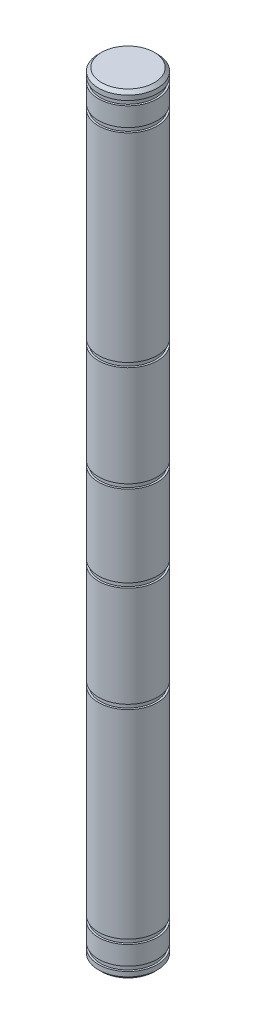
SolidWorks part; units mm, degrees
ref_plane "Front" through (0, 0, 0) normal (0, 0, 1) x (1, 0, 0)
ref_plane "Top" through (0, 0, 0) normal (0, 1, 0) x (1, 0, 0)
ref_plane "Right" through (0, 0, 0) normal (1, 0, 0) x (0, 0, -1)
ref_axis "side-side" through (80.9, 0, 0) along (-1, 0, 0)
ref_axis "up-down" through (0, 50, 0) along (0, -1, 0)
ref_axis "front-back" through (0, 0, -80.9) along (0, 0, 1)
sketch "Sketch1" plane through (0, 0, 0) normal (0, 0, 1) x (1, 0, 0)
  line L0 (-4.7625, 60.2234) -> (-4.7625, 57.1754)
  line L1 (0, 62.23) -> (-4.7625, 62.23)
  line L2 (0, 62.23) -> (0, -62.23)
  line L3 (0, -62.23) -> (-4.7625, -62.23)
  line L4 (-4.7625, 62.23) -> (-4.7625, 60.96)
  line L5 (-4.7625, 60.96) -> (-4.4577, 60.96)
  line L6 (-4.7625, -60.96) -> (-4.7625, -62.23)
  line L7 (-4.7625, 60.2234) -> (-4.4577, 60.2234)
  line L8 (-4.4577, 60.96) -> (-4.4577, 60.2234)
  line L9 (-4.7625, -60.2234) -> (-4.4577, -60.2234)
  line L10 (0, 62.23) -> (0, 13.3378) construction
  line L11 (-4.7625, -60.96) -> (-4.4577, -60.96)
  line L12 (-4.4577, -60.2234) -> (-4.4577, -60.96)
  line L13 (97.3746, 0) -> (-2.6254, 0) construction
  line L14 (-4.7625, 57.1754) -> (-4.4577, 57.1754)
  line L15 (-4.7625, 56.4388) -> (-4.7625, 24.2951)
  line L16 (-4.7625, 56.4388) -> (-4.4577, 56.4388)
  line L17 (-4.4577, 57.1754) -> (-4.4577, 56.4388)
  line L18 (-4.7625, -56.4388) -> (-4.4577, -56.4388)
  line L19 (-4.7625, -57.1754) -> (-4.7625, -60.2234)
  line L20 (-4.7625, -57.1754) -> (-4.4577, -57.1754)
  line L21 (-4.4577, -56.4388) -> (-4.4577, -57.1754)
  line L22 (50, 0) -> (-50, 0) construction
  line L23 (8.8317, 22.7965) -> (-9.0059, 22.7965) construction
  line L24 (-4.7625, 24.2951) -> (-4.4577, 24.2951)
  line L25 (-4.7625, 23.5585) -> (-4.7625, 7.3025)
  line L26 (-4.7625, 23.5585) -> (-4.4577, 23.5585)
  line L27 (-4.4577, 24.2951) -> (-4.4577, 23.5585)
  line L28 (-12.7, 7.9375) -> (12.7, 7.9375) construction
  line L29 (-4.7625, 7.3025) -> (-4.4577, 7.3025)
  line L30 (-22.0518, -22.7965) -> (-9.0059, -22.7965) construction
  line L31 (-4.7625, 6.5659) -> (-4.4577, 6.5659)
  line L32 (-4.4577, 7.3025) -> (-4.4577, 6.5659)
  line L33 (-4.7625, 6.5659) -> (-4.7625, -6.5659)
  line L34 (-4.7625, -7.3025) -> (-4.7625, -23.5585)
  line L35 (-4.7625, -6.5659) -> (-4.4577, -6.5659)
  line L36 (-4.7625, -24.2951) -> (-4.7625, -56.4388)
  line L37 (-4.7625, -7.3025) -> (-4.4577, -7.3025)
  line L38 (-4.4577, -6.5659) -> (-4.4577, -7.3025)
  line L39 (-4.7625, -23.5585) -> (-4.4577, -23.5585)
  line L41 (-4.7625, -24.2951) -> (-4.4577, -24.2951)
  line L42 (-4.4577, -23.5585) -> (-4.4577, -24.2951)
  line L43 (-22.0518, 17.8435) -> (-9.0059, 17.8435) construction
  line L44 (-9.0059, -17.8435) -> (-22.0518, -17.8435) construction
  dimension "D1" = 9.525
  dimension "D2" = 0.7366
  dimension "D3" = 1.27
  dimension "D4" = 120.4468
  dimension "D5" = 0.3048
  dimension "D6" = 62.23
  dimension "D7" = 62.23
  dimension "D8" = 3.048
  dimension "D9" = 0.762
  dimension "D10" = 0.635
  dimension "D11" = 0.762
  dimension "D12" = 10.541
  dimension "D13" = 10.541
revolve "Revolve1" add sketch "Sketch1" angle 360 about L10
chamfer "Chamfer1" distance 0.508 angle 45 2 edges at (-4.7625, -62.23, 0) (-4.7625, 62.23, 0)
